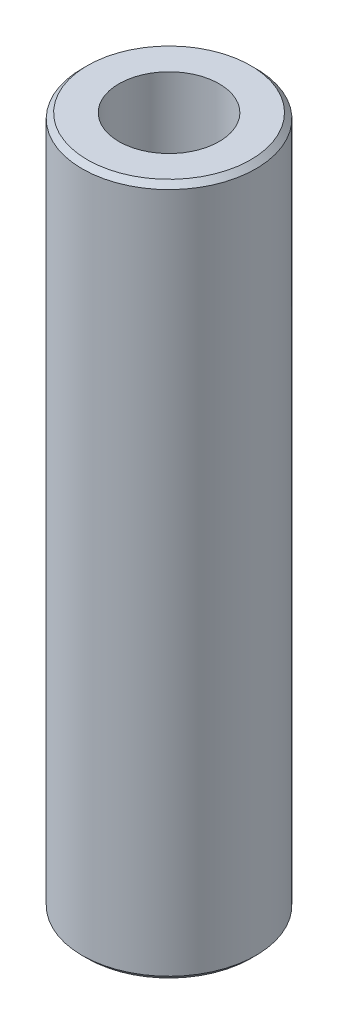
SolidWorks part; units mm, degrees
ref_plane "Front Plane" through (0, 0, 0) normal (0, 0, 1) x (1, 0, 0)
ref_plane "Top Plane" through (0, 0, 0) normal (0, 1, 0) x (1, 0, 0)
ref_plane "Right Plane" through (0, 0, 0) normal (1, 0, 0) x (0, 0, -1)
sketch "Sketch1" plane through (0, 0, 0) normal (0, 1, 0) x (1, 0, 0)
  circle A0 centre (0, 0) radius 35
  dimension "SHAFT_OD" = 70
extrude "Boss-Extrude1" add sketch "Sketch1" along normal blind 278.6747
sketch "Sketch2" plane through (0, 0, 0) normal (0, 1, 0) x (1, 0, 0)
  circle A0 centre (0, 0) radius 20.1894
  dimension "BORE_D" = 40.3788
extrude "Cut-Extrude1" cut sketch "Sketch2" along normal through all
chamfer "Chamfer1" distance 2.1015 angle 45 2 edges at (0, 278.6747, 35) (0, 0, 35)
